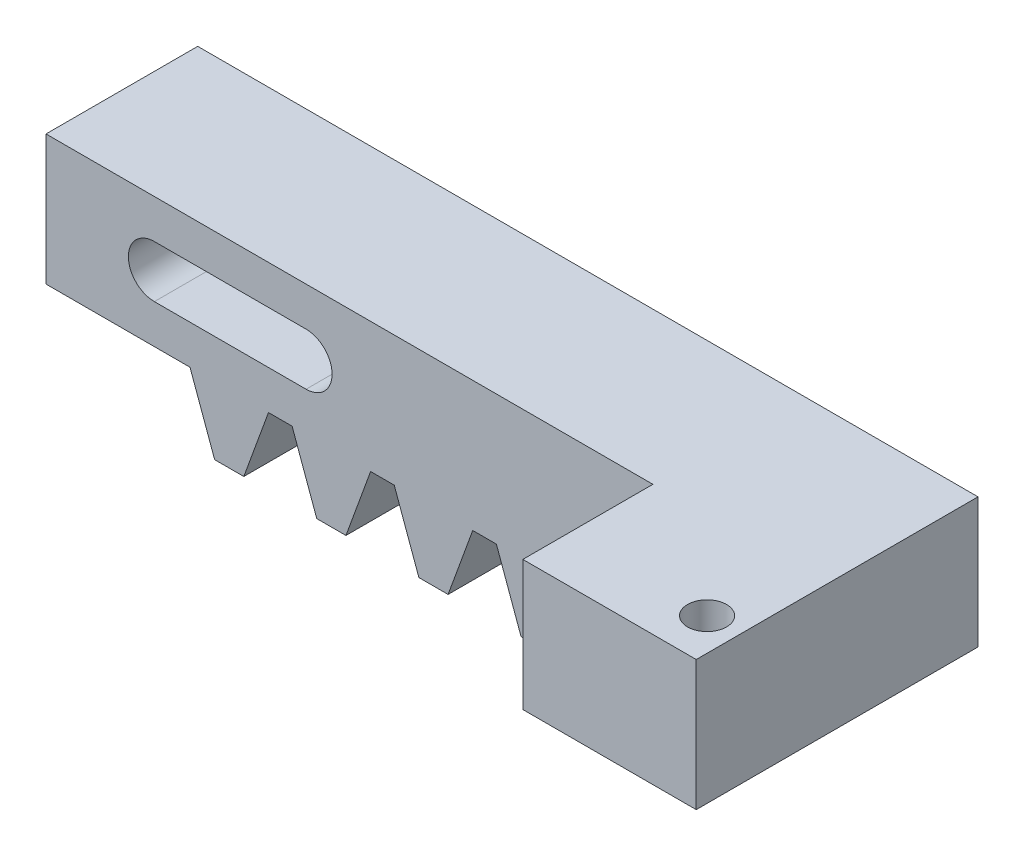
SolidWorks part; units mm, degrees
ref_plane "Front Plane" through (0, 0, 0) normal (0, 0, 1) x (1, 0, 0)
ref_plane "Top Plane" through (0, 0, 0) normal (0, 1, 0) x (1, 0, 0)
ref_plane "Right Plane" through (0, 0, 0) normal (1, 0, 0) x (0, 0, -1)
sketch "Sketch1" plane through (0, 0, 0) normal (0, 0, 1) x (1, 0, 0)
  line L0 (-16.7, 19.975) -> (19.3, 19.975)
  line L1 (19.3, 19.975) -> (19.3, 13.975)
  line L2 (19.3, 13.975) -> (17.1258, 13.975)
  line L3 (17.1258, 13.975) -> (15.9884, 10.85)
  line L4 (15.9884, 10.85) -> (14.6421, 10.85)
  line L5 (14.6421, 10.85) -> (13.5047, 13.975)
  line L6 (13.5047, 13.975) -> (12.4134, 13.975)
  line L7 (12.4134, 13.975) -> (11.276, 10.85)
  line L8 (11.276, 10.85) -> (9.9297, 10.85)
  line L9 (9.9297, 10.85) -> (8.7923, 13.975)
  line L10 (8.7923, 13.975) -> (7.701, 13.975)
  line L11 (7.701, 13.975) -> (6.5636, 10.85)
  line L12 (6.5636, 10.85) -> (5.2174, 10.85)
  line L13 (5.2174, 10.85) -> (4.0799, 13.975)
  line L14 (4.0799, 13.975) -> (2.9886, 13.975)
  line L15 (2.9886, 13.975) -> (1.8512, 10.85)
  line L16 (1.8512, 10.85) -> (0.505, 10.85)
  line L17 (0.505, 10.85) -> (-0.6324, 13.975)
  line L18 (-0.6324, 13.975) -> (-1.7238, 13.975)
  line L19 (-1.7238, 13.975) -> (-2.8612, 10.85)
  line L20 (-2.8612, 10.85) -> (-4.2074, 10.85)
  line L21 (-4.2074, 10.85) -> (-5.3448, 13.975)
  line L22 (-5.3448, 13.975) -> (-6.4361, 13.975)
  line L23 (-6.4361, 13.975) -> (-7.5735, 10.85)
  line L24 (-7.5735, 10.85) -> (-8.9198, 10.85)
  line L25 (-8.9198, 10.85) -> (-10.0572, 13.975)
  line L26 (-10.0572, 13.975) -> (-16.7, 13.975)
  line L27 (-16.7, 13.975) -> (-16.7, 19.975)
extrude "Boss-Extrude1" add sketch "Sketch1" along normal blind 7 from offset 13.5
sketch "Sketch2" plane through (0, 0, 0) normal (0, 0, 1) x (1, 0, 0)
  line L0 (11.3, 13.975) -> (19.3, 13.975)
  line L1 (19.3, 13.975) -> (19.3, 19.975)
  line L2 (19.3, 19.975) -> (11.3, 19.975)
  line L3 (11.3, 19.975) -> (11.3, 13.975)
extrude "Boss-Extrude2" add sketch "Sketch2" along normal blind 6 from offset 20.5
sketch "Sketch3" plane through (0, 0, 0) normal (0, 1, 0) x (1, 0, 0)
  circle A0 centre (17.8, -24.5) radius 0.9
extrude "Cut-Extrude1" cut sketch "Sketch3" against normal through all and the other way through all
sketch "Sketch4" plane through (0, 0, 0) normal (0, 0, 1) x (1, 0, 0)
  line L0 (-11.7, 15.775) -> (-4.7, 15.775)
  line L1 (-4.7, 15.775) -> (-4.7, 18.175)
  line L2 (-4.7, 18.175) -> (-11.7, 18.175)
  line L3 (-11.7, 18.175) -> (-11.7, 15.775)
extrude "Cut-Extrude2" cut sketch "Sketch4" against normal through all and the other way through all
sketch "Sketch5" plane through (0, 0, 0) normal (0, 0, 1) x (1, 0, 0)
  circle A0 centre (-11.7, 16.975) radius 1.2
  circle A1 centre (-4.7, 16.975) radius 1.2
extrude "Cut-Extrude3" cut sketch "Sketch5" against normal through all and the other way through all
